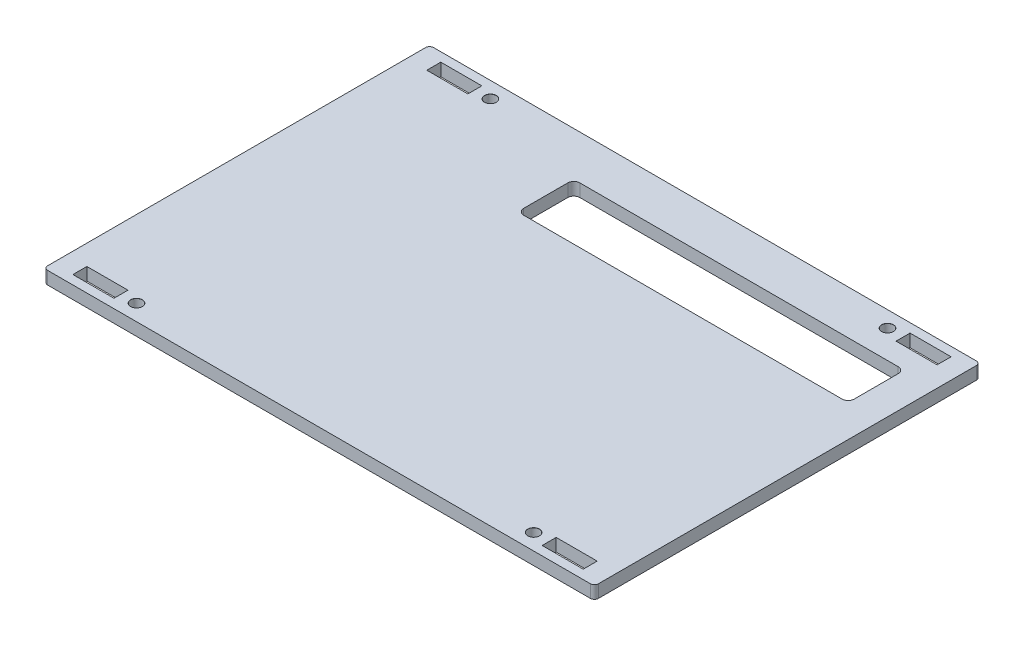
SolidWorks part; units mm, degrees
material "MDF"
ref_plane "Front Plane" through (0, 0, 0) normal (0, 0, 1) x (1, 0, 0)
ref_plane "Top Plane" through (0, 0, 0) normal (0, 1, 0) x (1, 0, 0)
ref_plane "Right Plane" through (0, 0, 0) normal (1, 0, 0) x (0, 0, -1)
sketch "Sketch1" plane through (0, 0, 0) normal (0, 1, 0) x (1, 0, 0)
  line L1 (-68.745, -48.1725) -> (68.745, -48.1725)
  line L2 (-68.745, -48.1725) -> (-68.745, 48.1725)
  line L3 (-68.745, 48.1725) -> (68.745, 48.1725)
  line L4 (68.745, -48.1725) -> (68.745, 48.1725)
  line L5 (-68.745, -48.1725) -> (68.745, 48.1725) construction
  line L6 (-68.745, 48.1725) -> (68.745, -48.1725) construction
  line L7 (-68.745, -44.1725) -> (68.745, -44.1725) construction
  line L8 (-68.745, -44.1725) -> (-68.745, 44.1725)
  line L9 (-68.745, 44.1725) -> (68.745, 44.1725) construction
  line L10 (68.745, -44.1725) -> (68.745, 44.1725)
  line L11 (-68.745, -44.1725) -> (68.745, 44.1725) construction
  line L12 (-68.745, 44.1725) -> (68.745, -44.1725) construction
  line L13 (-63.695, 42.4262) -> (-53.445, 42.4262)
  line L14 (-63.695, 42.4262) -> (-63.695, 45.9187)
  line L15 (-63.695, 45.9187) -> (-53.445, 45.9187)
  line L16 (-53.445, 42.4262) -> (-53.445, 45.9187)
  line L17 (-63.695, 42.4262) -> (-53.445, 45.9187) construction
  line L18 (-63.695, 45.9187) -> (-53.445, 42.4262) construction
  circle A0 centre (-49.57, 44.1725) radius 2.5
  point P0 (0, 0)
  point P6 (0, 0)
  point P11 (-58.57, 44.1725)
  dimension "D8" = 5
  dimension "D1" = 88.345
  dimension "D2" = 137.49
  dimension "D3" = 4
  dimension "D4" = 10.175
  dimension "D5" = 10.25
  dimension "D6" = 3.4925
  dimension "D7" = 19.175
extrude "Boss-Extrude1" add sketch "Sketch1" along normal blind 3.175 contours L1 L4 L3 L2 A0 L16 L13 L14 L15 | L13 L16 L15 L14 | A0 region at (0.2327, 0, 0.1856) region at (-58.57, 0, -44.1725) region at (-49.57, 0, -44.1725)
extrude "Cut-Extrude1" cut sketch "Sketch1<3>" against normal through all both and the other way through all contours L13 L16 L15 L14 region at (-58.57, 0, -44.1725)
sketch "Sketch1<3>" plane through (0, 0, 0) normal (0, 1, 0) x (1, 0, 0) same geometry as "Sketch1"
sketch "Sketch2" plane through (0, 3.175, 0) normal (0, 1, 0) x (1, 0, 0)
  point P0 (-49.57, 44.1725)
hole_wizard "M2.5 Clearance Hole1" positions "Sketch2" profile "Sketch3" hole size "M2.5" standard "ANSI Metric" end condition through all
sketch "Sketch3" plane through (-49.57, 3.175, -44.1725) normal (1, 0, 0) x (0, 0, 1)
  line L0 (0, 0) -> (0, 3.175)
  line L1 (0, 3.175) -> (1.45, 3.175)
  line L2 (1.45, 3.175) -> (1.45, 0.021)
  line L3 (1.45, 0.021) -> (1.475, 0)
  line L5 (1.475, 0) -> (0, 0)
  line L6 (-1.45, 0.021) -> (-1.475, 0) construction
  line L11 (0, -6.35) -> (0, 107.95) construction
  dimension "Thru Hole Dia." = 2.9
  dimension "Thru Hole Depth" = 3.175
  dimension "Near C'Sink Dia." = 2.95
  dimension "Near C'Sink Angle" = 100
mirror "Mirror1" about plane through (0, 0, 0) normal (1, 0, 0) of "M2.5 Clearance Hole1", "Cut-Extrude1" second plane through (0, 0, 0) second plane normal (0, 0, 1)
sketch "Sketch4" plane through (0, 3.175, 0) normal (0, 1, 0) x (1, 0, 0)
  line L0 (68.745, -48.1725) -> (68.745, 48.1725) construction
  line L1 (-21.745, 37.1725) -> (60.745, 37.1725)
  line L2 (-21.745, 37.1725) -> (-21.745, 23.1725)
  line L3 (-21.745, 23.1725) -> (60.745, 23.1725)
  line L4 (60.745, 37.1725) -> (60.745, 23.1725)
  line L5 (-68.745, -48.1725) -> (-68.745, 48.1725) construction
  line L6 (-68.745, 48.1725) -> (68.745, 48.1725) construction
  dimension "D1" = 8
  dimension "D2" = 47
  dimension "D3" = 11
  dimension "D4" = 14
extrude "Cut-Extrude2" cut sketch "Sketch4" against normal through all both and the other way through all
fillet "Fillet1" radius 1.5 4 edges at (-21.745, 1.5875, -23.1725) (60.745, 1.5875, -23.1725) (60.745, 1.5875, -37.1725) (-21.745, 1.5875, -37.1725)
fillet "Fillet2" radius 1 4 edges at (68.745, 1.5875, 48.1725) (-68.745, 1.5875, 48.1725) (-68.745, 1.5875, -48.1725) (68.745, 1.5875, -48.1725)
